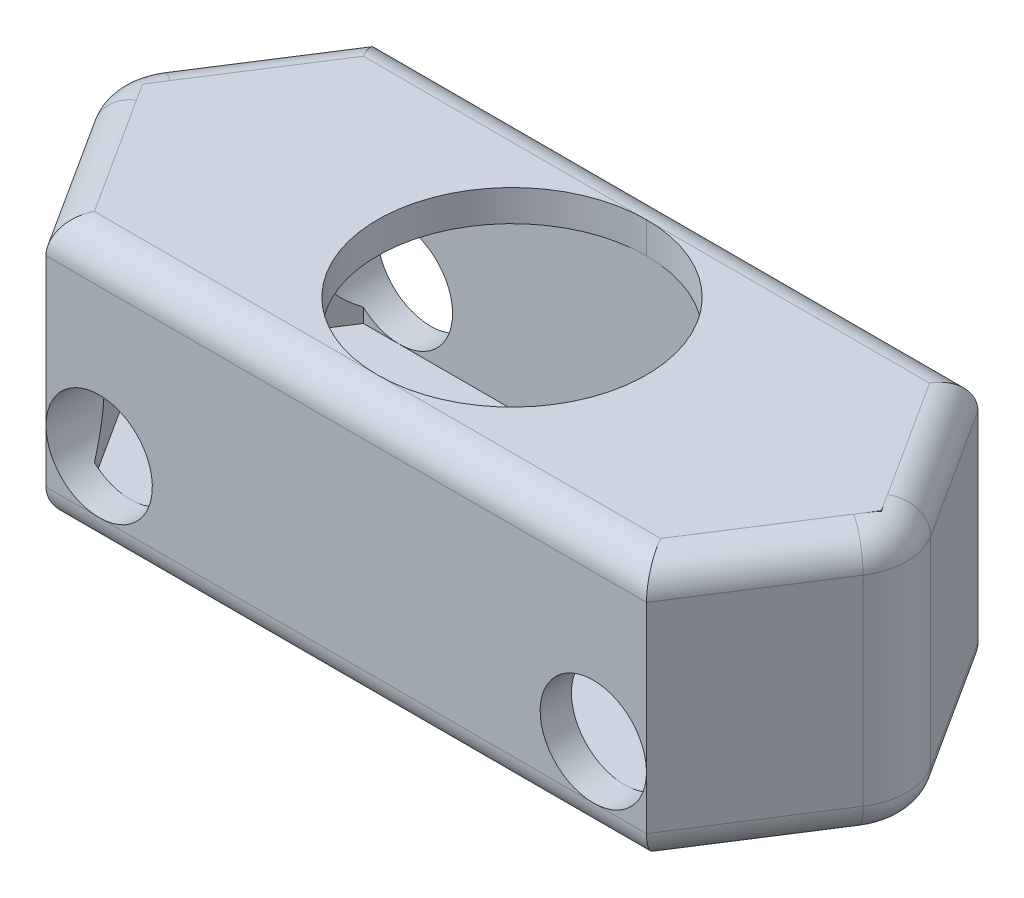
SolidWorks part; units mm, degrees
ref_plane "Front Plane" through (0, 0, 0) normal (0, 0, 1) x (1, 0, 0)
ref_plane "Top Plane" through (0, 0, 0) normal (0, 1, 0) x (1, 0, 0)
ref_plane "Right Plane" through (0, 0, 0) normal (1, 0, 0) x (0, 0, -1)
sketch "Sketch1" plane through (0, 0, 0) normal (0, 1, 0) x (1, 0, 0)
  line L1 (-48, 26.5) -> (48, 26.5)
  line L2 (-48, 26.5) -> (-48, -26.5)
  line L3 (-48, -26.5) -> (48, -26.5)
  line L4 (48, 26.5) -> (48, -26.5)
  line L5 (-48, 26.5) -> (48, -26.5) construction
  line L6 (-48, -26.5) -> (48, 26.5) construction
  point P0 (0, 0)
  dimension "D1" = 53
  dimension "D2" = 96
extrude "Boss-Extrude1" add sketch "Sketch1" along normal blind 42
sketch "Sketch3" plane through (0, 0, 0) normal (0, -1, 0) x (1, 0, 0)
  line L0 (48, -26.5) -> (65, 0)
  line L1 (65, 0) -> (48, 26.5)
  line L2 (48, 26.5) -> (48, -26.5)
  line L3 (-48, 26.5) -> (-65, 0)
  line L4 (-65, 0) -> (-48, -26.5)
  line L5 (-48, -26.5) -> (-48, 26.5)
  line L6 (-83.7177, 0) -> (95.9582, 0) construction
  dimension "D1" = 17
  dimension "D3" = 17
  dimension "D4" = 130
extrude "Boss-Extrude2" add sketch "Sketch3" against normal blind 42
shell "Shell5" thickness 5 removed face at (0, 42, 0)
sketch "Sketch6" plane through (0, 42, 0) normal (0, 1, 0) x (1, 0, 0)
  line L0 (-48.2426, 21.5) -> (48.7574, 21.5)
  line L2 (-48.2426, 21.5) -> (-61, 0)
  line L3 (-61, 0) -> (-48.2426, -21.5)
  line L5 (-82.9427, 0) -> (81.0316, 0) construction
  line L7 (48.7574, 21.5) -> (61.5147, 0)
  line L8 (61.5147, 0) -> (48.7574, -21.5)
  line L9 (-48.2426, -21.5) -> (48.7574, -21.5)
  circle A2 centre (0, 0) radius 21.5
  line M19 (45.2671, 21.5) -> (59.0596, 0)
  line M21 (59.0596, 0) -> (45.2671, -21.5)
  line M23 (45.2671, -21.5) -> (-45.2671, -21.5)
  line M25 (-45.2671, -21.5) -> (-59.0596, 0)
  line M27 (-59.0596, 0) -> (-45.2671, 21.5)
  line M29 (-45.2671, 21.5) -> (45.2671, 21.5)
  dimension "D3" = 25
  dimension "D4" = 97
  dimension "D1" = 43
  dimension "D2" = 25
  dimension "D5" = 97
  dimension "D6" = 25
  dimension "D7" = 25
  dimension "D8" = 61
sketch "Sketch8" plane through (0, 5, 0) normal (0, 1, 0) x (1, 0, 0)
  text T0 "<b>Group 4</b>"
extrude "Cut-Extrude2" cut sketch "Sketch8" against normal blind 1
fillet "Fillet1" radius 10 2 edges at (65, 21, 0) (-65, 21, 0)
fillet "Fillet3" radius 5 16 edges at (54.7681, 0, 15.9498) (63.1192, 0, 0) (-54.7681, 0, -15.9498) (-63.1192, 0, 0) (54.7681, 42, 15.9498) (63.1192, 42, 0) (-54.7681, 42, -15.9498) (-63.1192, 42, 0) (54.7681, 0, -15.9498) (0, 0, -26.5) (-54.7681, 0, 15.9498) (0, 0, 26.5) (54.7681, 42, -15.9498) (0, 42, -26.5) (-54.7681, 42, 15.9498) (0, 42, 26.5)
sketch "Sketch10" plane through (0, 0, 26.5) normal (0, 0, 1) x (1, 0, 0)
  line L2 (-48, 5) -> (48, 5) construction
  line L3 (-48, 37) -> (-48, 5) construction
  line L4 (48, 37) -> (48, 5) construction
  circle A0 centre (-39.5, 13.5) radius 8.5
  circle A1 centre (39.5, 13.5) radius 8.5
  dimension "D1" = 17
  dimension "D2" = 17
  dimension "D3" = 8.5
  dimension "D4" = 8.5
extrude "Cut-Extrude3" cut sketch "Sketch10" against normal through all
extrude "Boss-Extrude3" add sketch "Sketch6" against normal blind 5 separate body contours L5 A2 M27 M29 | L5 L9 A2 M25 | A2 L5 L0 M19 | L5 A2 M23 M21 region at (-34.423, 42, -10.8274) region at (34.423, 42, -10.8274) region at (-34.423, 42, 10.8274) region at (34.423, 42, 10.8274)
